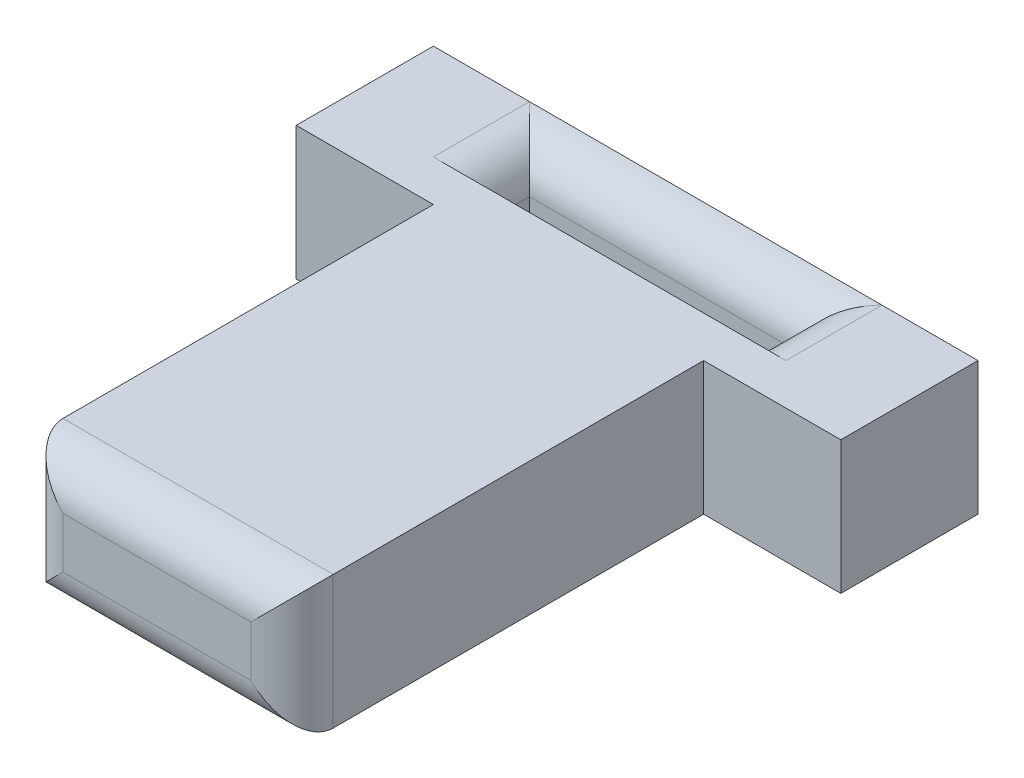
SolidWorks part; units mm, degrees
ref_plane "Front Plane" through (0, 0, 0) normal (0, 0, 1) x (1, 0, 0)
ref_plane "Top Plane" through (0, 0, 0) normal (0, 1, 0) x (1, 0, 0)
ref_plane "Right Plane" through (0, 0, 0) normal (1, 0, 0) x (0, 0, -1)
sketch "Sketch1" plane through (0, 0, 0) normal (0, 0, 1) x (1, 0, 0)
  line L1 (9.85, 4.85) -> (-9.85, 4.85)
  line L2 (9.85, 4.85) -> (9.85, -4.85)
  line L3 (9.85, -4.85) -> (-9.85, -4.85)
  line L4 (-9.85, 4.85) -> (-9.85, -4.85)
  line L5 (9.85, 4.85) -> (-9.85, -4.85) construction
  line L6 (9.85, -4.85) -> (-9.85, 4.85) construction
  point P0 (0, 0)
  dimension "D1" = 19.7
  dimension "D2" = 9.7
extrude "Boss-Extrude1" add sketch "Sketch1" along normal blind 30
sketch "Sketch2" plane through (0, 0, 0) normal (0, 0, -1) x (-1, 0, 0)
  line L0 (-9.85, -4.85) -> (-9.85, 4.85) construction
  line L1 (19.85, 4.85) -> (-19.85, 4.85)
  line L2 (19.85, 4.85) -> (19.85, -4.85)
  line L3 (19.85, -4.85) -> (-19.85, -4.85)
  line L4 (-19.85, 4.85) -> (-19.85, -4.85)
  line L5 (19.85, 4.85) -> (-19.85, -4.85) construction
  line L6 (19.85, -4.85) -> (-19.85, 4.85) construction
  line L7 (-9.85, 4.85) -> (9.85, 4.85) construction
  point P0 (0, 0)
  dimension "D1" = 10
  dimension "D2" = 0
extrude "Boss-Extrude2" add sketch "Sketch2" along normal blind 10
sketch "Sketch3" plane through (0, 4.85, 0) normal (0, 1, 0) x (1, 0, 0)
  line L0 (-19.85, 10) -> (19.85, 10) construction
  line L1 (9.85, 7) -> (-9.85, 7)
  line L2 (9.85, 7) -> (9.85, 3)
  line L3 (9.85, 3) -> (-9.85, 3)
  line L4 (-9.85, 7) -> (-9.85, 3)
  line L5 (9.85, 7) -> (-9.85, 3) construction
  line L6 (9.85, 3) -> (-9.85, 7) construction
  line L7 (9.85, 0) -> (19.85, 0) construction
  line L8 (9.85, -30) -> (9.85, 0) construction
  line L9 (-9.85, -30) -> (-9.85, 0) construction
  point P0 (0, 5)
  dimension "D1" = 3
  dimension "D2" = 3
  dimension "D3" = 0
  dimension "D4" = 0
extrude "Cut-Extrude1" cut sketch "Sketch3" against normal blind 10
fillet "Fillet1" radius 3 6 edges at (-9.85, -4.85, -5) (9.85, -4.85, -5) (9.85, 4.85, -5) (-9.85, 4.85, -5) (0, -4.85, -7) (0, 4.85, -7)
fillet "Fillet2" radius 3 4 edges at (0, 4.85, 30) (9.85, 0, 30) (0, -4.85, 30) (-9.85, 0, 30)
